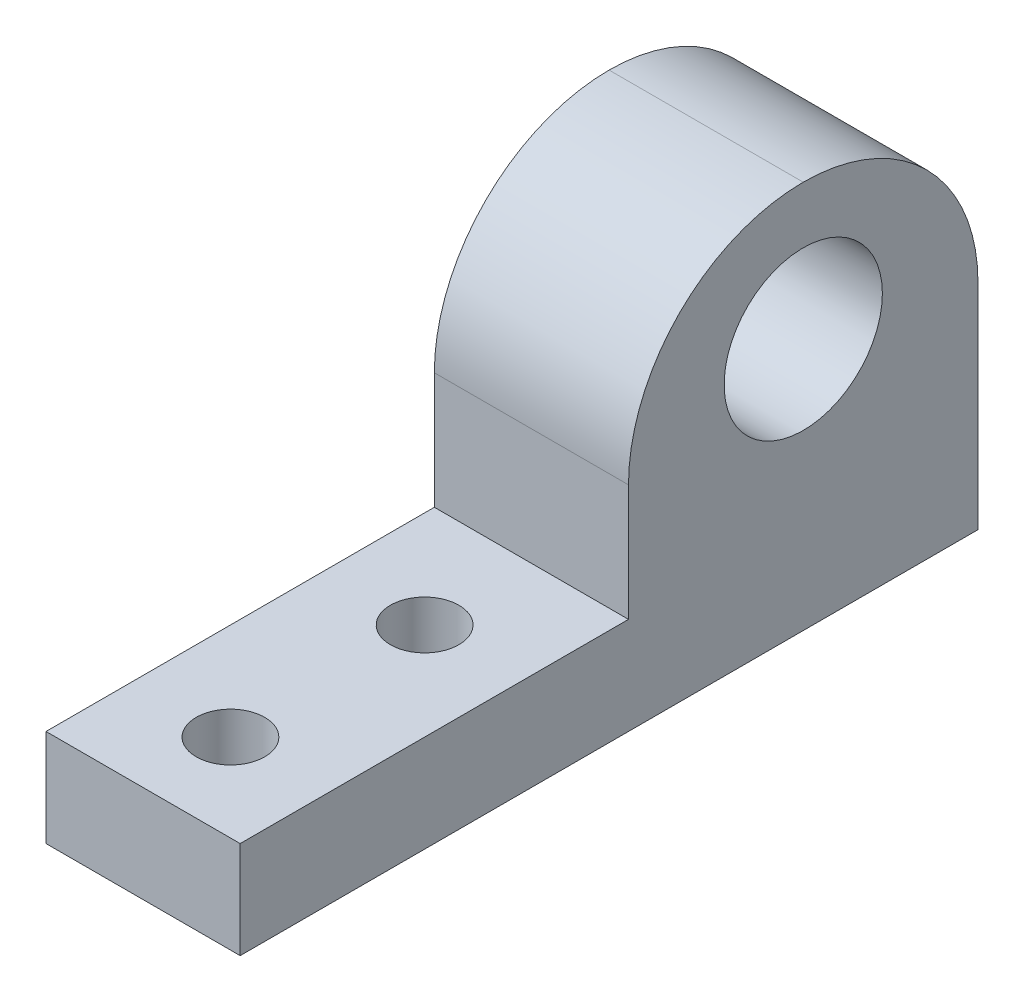
SolidWorks part; units mm, degrees
ref_plane "前视基准面" through (0, 0, 0) normal (0, 0, 1) x (1, 0, 0)
ref_plane "上视基准面" through (0, 0, 0) normal (0, 1, 0) x (1, 0, 0)
ref_plane "右视基准面" through (0, 0, 0) normal (1, 0, 0) x (0, 0, -1)
sketch "草图2" plane through (0, 0, 0) normal (0, 1, 0) x (1, 0, 0)
  line L1 (-7.1892, 6.5946) -> (2.8108, 6.5946)
  line L2 (-7.1892, 6.5946) -> (-7.1892, -31.4054)
  line L4 (2.8108, 6.5946) -> (2.8108, -31.4054)
  line L9 (-2.1892, 10.0292) -> (-2.1892, -32.8858) construction
  line L10 (2.8108, -31.4054) -> (-7.1892, -31.4054)
  circle A2 centre (-2.1892, -26.9054) radius 1.7636
  circle A3 centre (-2.1892, -16.9054) radius 1.7636
  dimension "D3" = 10
  dimension "D4" = 4.5
  dimension "D1" = 10
  dimension "D2" = 38
extrude "凸台-拉伸2" add sketch "草图2" along normal blind 5
sketch "草图3" plane through (0, 5, 0) normal (0, 1, 0) x (1, 0, 0)
  line L0 (2.8108, -31.4054) -> (2.8108, 6.5946) construction
  line L1 (-7.1892, 6.5946) -> (2.8108, 6.5946)
  line L2 (-7.1892, 6.5946) -> (-7.1892, -11.4054)
  line L3 (-7.1892, -11.4054) -> (2.8108, -11.4054)
  line L4 (2.8108, 6.5946) -> (2.8108, -11.4054)
  dimension "D1" = 18
extrude "凸台-拉伸3" add sketch "草图3" along normal blind 15
fillet "圆角1" radius 9 2 edges at (-2.1892, 20, 11.4054) (-2.1892, 20, -6.5946)
sketch "草图4" plane through (2.8108, 0, 0) normal (1, 0, 0) x (0, 0, -1)
  line L2 (-2.4054, 26.8344) -> (-2.4054, -4.8434) construction
  line L3 (-11.4054, 11) -> (-11.4054, 5) construction
  line L4 (6.5946, 11) -> (6.5946, 0) construction
  line L5 (-31.4054, 0) -> (6.5946, 0) construction
  circle A0 centre (-2.4054, 13) radius 4.075
  dimension "D1" = 8.15
  dimension "D2" = 13
extrude "切除-拉伸1" cut sketch "草图4" against normal blind 20
